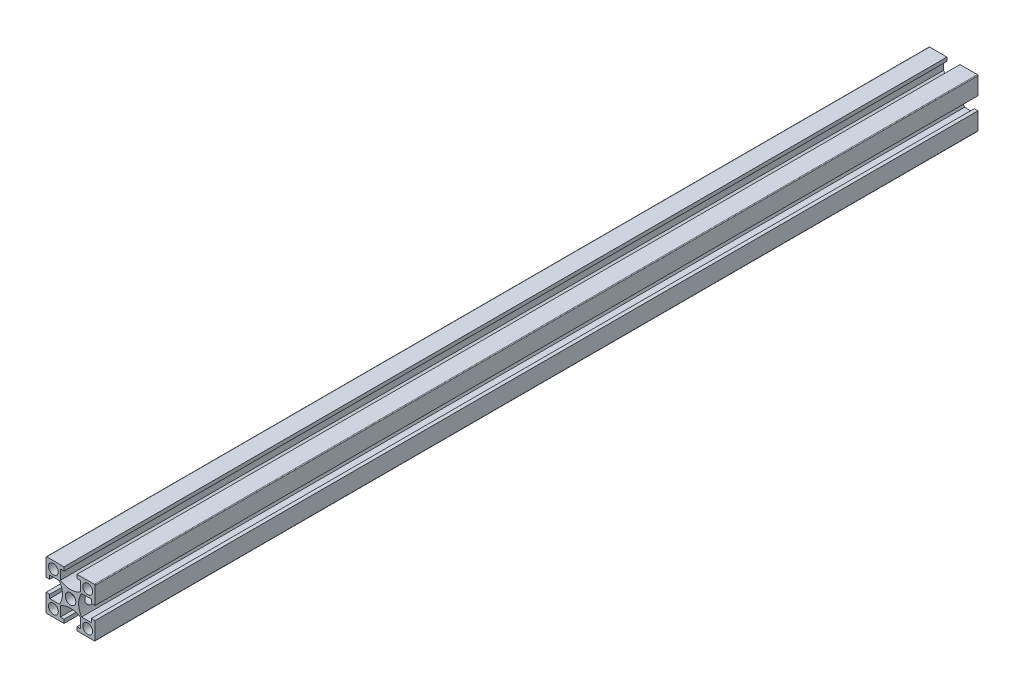
SolidWorks part; units mm, degrees
material "3.0255 (EN-AW 1350A)"
ref_plane "정면" through (0, 0, 0) normal (0, 0, 1) x (1, 0, 0)
ref_plane "윗면" through (0, 0, 0) normal (0, 1, 0) x (1, 0, 0)
ref_plane "우측면" through (0, 0, 0) normal (1, 0, 0) x (0, 0, -1)
sketch "스케치1" plane through (0, 0, 0) normal (0, 0, 1) x (1, 0, 0)
  line L0 (0, 32.0265) -> (0, -31.6588) construction
  line L1 (-10, 10) -> (-10, -10)
  line L2 (-10, 10) -> (10, 10)
  line L3 (-10, 2.65) -> (-8.5, 2.65)
  line L4 (13.6618, 0) -> (-11.6993, 0) construction
  line L5 (-8.5, 2.65) -> (-8.5, 4.15)
  line L6 (-8.5, 4.15) -> (-4.5032, 4.15)
  line L7 (-10, -2.65) -> (-8.5, -2.65)
  line L8 (-8.5, -2.65) -> (-8.5, -4.15)
  line L9 (-8.5, -4.15) -> (-4.5032, -4.15)
  line L10 (-10, -10) -> (10, -10)
  line L11 (10, 10) -> (10, -10)
  circle A0 centre (-7, 7) radius 2
  circle A1 centre (-7, -7) radius 2
  arc A2 (-4.5032, 4.15) -> (-4.5032, -4.15) centre (-11.0587, 0) cw
  circle A3 centre (0, 0) radius 2.15
  circle A4 centre (7, 7) radius 2
  circle A5 centre (7, -7) radius 2
  point P21 (-10, 0)
  point P23 (-3.3, 0)
  point P31 (0, -10)
  point P32 (0, 10)
  dimension "D3" = 4
  dimension "D9" = 6.7
  dimension "D10" = 4.3
  dimension "D11" = 7.7587
  dimension "D1" = 20
  dimension "D2" = 20
  dimension "D4" = 14
  dimension "D5" = 14
  dimension "D6" = 5.3
  dimension "D7" = 8.3
  dimension "D8" = 1.5
extrude "보스-돌출1" add sketch "스케치1" along normal blind 360 contours A0 | A4 | A3 | A5 | A1 | A2 L6 L5 L3 L1 L7 L8 L9 | L2 L11 L10 L1 region at (-6.6069, 0, 0) region at (-7, 7, 0) region at (-7, -7, 0) region at (0, 0, 0) region at (7, 7, 0) region at (7, -7, 0)
extrude "컷-돌출1" cut sketch "스케치1<3>" along normal up to next contours A2 L6 L5 L3 L1 L7 L8 L9 region at (-6.6069, 0, 0)
sketch "스케치1<3>" plane through (0, 0, 0) normal (0, 0, 1) x (1, 0, 0) same geometry as "스케치1"
pattern_circular "원형 패턴1" count 4 over 360 about axis through (0, 0, 360) along (0, 0, -1) of "컷-돌출1" reverse direction yes
fillet "필렛1" radius 0.3 4 edges at (10, -10, 180) (-10, -10, 180) (-10, 10, 180) (10, 10, 180)
sketch "스케치2" plane through (0, 0, 0) normal (1, 0, 0) x (0, 0, -1)
  line L0 (0, -2.65) -> (0, -9.7) construction
  line L1 (-360, 4.15) -> (-360, -4.15) construction
  circle A0 centre (-5, 0) radius 2.5
  circle A1 centre (-355, 0) radius 2.5
  dimension "D1" = 5
  dimension "D4" = 5
  dimension "D2" = 5
  dimension "D3" = 5
extrude "컷-돌출2" cut sketch "스케치2" against normal through all both and the other way through all contours A0 | A1
sketch "스케치3" plane through (10, 0, 0) normal (1, 0, 0) x (0, 0, -1)
  line L0 (-33.65, 9.7) -> (-33.65, -9.7) construction
  line L1 (0, 9.7) -> (-360, 9.7) construction
  line L2 (-360, -9.7) -> (0, -9.7) construction
  line L3 (-166.62, 9.7) -> (-166.62, -9.7) construction
  line L4 (-326.1, 9.7) -> (-326.1, -9.7) construction
  line L5 (0, -2.65) -> (0, -9.7) construction
  line L6 (-346.1, 9.7) -> (-346.1, -9.7) construction
  line L7 (-186.62, 9.7) -> (-186.62, -9.7) construction
  line L8 (-53.65, 9.7) -> (-53.65, -9.7) construction
  circle A0 centre (-64.65, 0) radius 2.5
  circle A1 centre (-155.62, 0) radius 2.5
  circle A2 centre (-197.62, 0) radius 2.5
  circle A3 centre (-315.1, 0) radius 2.5
  dimension "D7" = 11
  dimension "D8" = 11
  dimension "D1" = 33.65
  dimension "D2" = 166.62
  dimension "D3" = 326.1
  dimension "D10" = 11
  dimension "D5" = 20
  dimension "D4" = 20
  dimension "D6" = 20
extrude "컷-돌출3" [suppressed] cut sketch "스케치3" against normal through all
sketch "스케치4" plane through (10, 0, 0) normal (1, 0, 0) x (0, 0, -1)
  line L0 (-326.35, 9.7) -> (-326.35, -9.7) construction
  line L1 (0, 9.7) -> (-360, 9.7) construction
  line L2 (-360, -9.7) -> (0, -9.7) construction
  line L3 (-193.38, 9.7) -> (-193.38, -9.7) construction
  line L4 (-33.9, 9.7) -> (-33.9, -9.7) construction
  line L5 (-360, 9.7) -> (-360, 2.65) construction
  line L6 (-306.35, 9.7) -> (-306.35, -9.7) construction
  line L7 (-173.38, 9.7) -> (-173.38, -9.7) construction
  line L8 (-13.9, 9.7) -> (-13.9, -9.7) construction
  circle A4 centre (-316.35, 0) radius 2.5
  circle A5 centre (-183.38, 0) radius 2.5
  circle A6 centre (-23.9, 0) radius 2.5
  dimension "D7" = 10
  dimension "D1" = 33.65
  dimension "D2" = 166.62
  dimension "D3" = 326.1
  dimension "D4" = 20
  dimension "D5" = 20
  dimension "D6" = 20
extrude "컷-돌출4" cut sketch "스케치4" against normal through all
